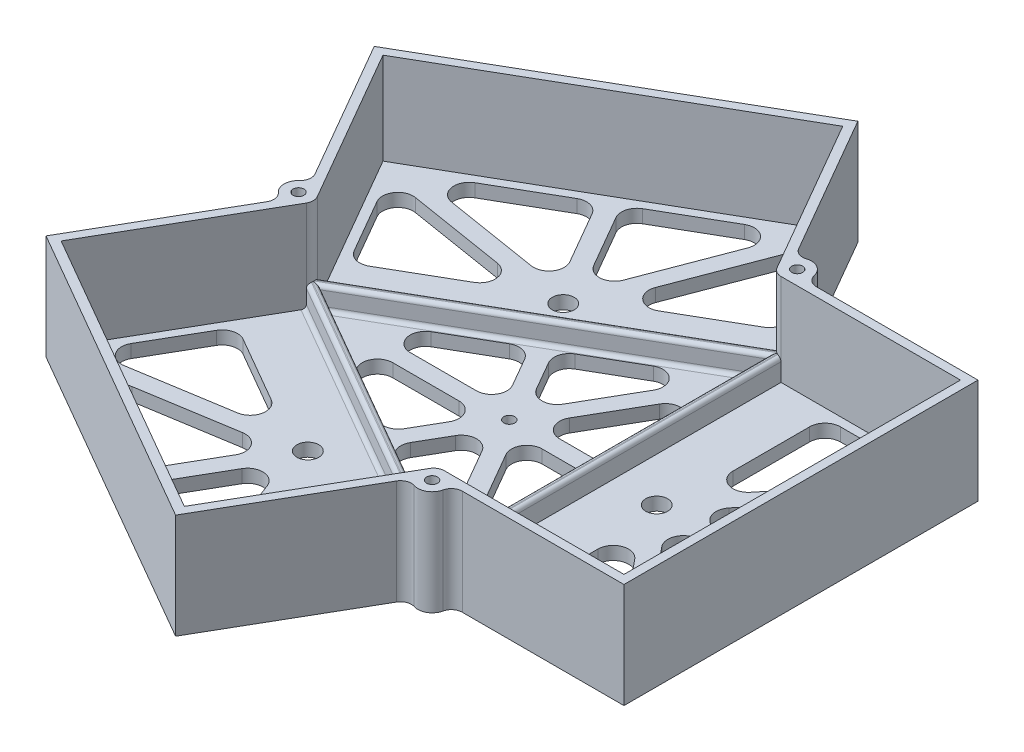
SolidWorks part; units mm, degrees
ref_plane "Front Plane" through (0, 0, 0) normal (0, 0, 1) x (1, 0, 0)
ref_plane "Top Plane" through (0, 0, 0) normal (0, 1, 0) x (1, 0, 0)
ref_plane "Right Plane" through (0, 0, 0) normal (1, 0, 0) x (0, 0, -1)
sketch "Sketch1" plane through (0, 0, 0) normal (0, 1, 0) x (1, 0, 0)
  line L0 (19.5158, -90.1492) -> (5.5625, -53.4677)
  line L5 (23.4295, -18.521) -> (22.1795, -20.6861)
  line L6 (85.5432, -56.1036) -> (56.6565, -56.1036) construction
  line L7 (89.5432, -60.1036) -> (89.5432, 20.8964)
  line L8 (-10.5648, -77.401) -> (24.5092, -97.651)
  line L9 (-27.1955, -27.3848) -> (-27.1955, -21.6036)
  line L10 (-10.5648, -77.401) -> (-45.6389, -57.151)
  line L11 (-45.6389, -57.151) -> (-29.1955, -28.6702)
  line L12 (-45.6389, 17.9439) -> (-29.1955, -10.5369)
  line L13 (24.5092, 58.4439) -> (40.9526, 29.9631)
  line L14 (-27.1955, -19.6036) -> (20.4951, -19.6036)
  line L19 (-45.6389, 17.9439) -> (24.5092, 58.4439)
  line L20 (89.5432, 20.8964) -> (56.6565, 20.8964)
  line L21 (89.5432, -60.1036) -> (56.6565, -60.1036)
  line L22 (24.5092, -97.651) -> (40.9526, -69.1702)
  line L23 (41.0658, 27.5883) -> (46.0725, 24.6977)
  line L24 (5.2031, -46.0901) -> (-27.1955, -27.3848)
  line L25 (47.8045, 23.6977) -> (23.9592, -17.6036)
  line L26 (-29.1955, -28.6702) -> (-29.1955, -10.5369)
  line L27 (0.0674, -47.7438) -> (-26.6748, -32.3042)
  line L28 (58.5432, -25.2243) -> (58.5432, -56.1036)
  line L29 (40.9526, -69.1702) -> (56.6565, -60.1036)
  line L34 (40.9526, 29.9631) -> (56.6565, 20.8964)
  line L35 (54.5432, -21.6036) -> (54.5432, -59.0142)
  line L36 (9.8029, 14.1574) -> (36.5451, 29.5971)
  line L37 (49.5366, 22.6977) -> (54.5432, 19.8071)
  line L38 (54.5432, -59.0142) -> (49.5366, -61.9048)
  line L39 (8.6672, 8.883) -> (41.0658, 27.5883)
  line L40 (47.8045, -62.9048) -> (23.9592, -21.6036)
  line L41 (21.6498, -17.6036) -> (7.2251, 7.3808)
  line L42 (21.5545, -19.6036) -> (24.0545, -19.6036)
  line L43 (21.6498, -21.6036) -> (7.2251, -46.5879)
  line L44 (23.4295, -20.6861) -> (22.1795, -18.521)
  line L45 (-26.6748, -6.9029) -> (0.0674, 8.5367)
  line L46 (58.5432, 16.8964) -> (58.5432, -13.9828)
  line L47 (36.5451, -68.8042) -> (9.8029, -53.3646)
  line L48 (-27.1955, -11.8224) -> (5.2031, 6.883)
  line L49 (54.5432, 19.8071) -> (54.5432, -17.6036)
  line L50 (41.0658, -66.7954) -> (8.6672, -48.0901)
  line L51 (46.0725, 24.6977) -> (22.8045, -15.6036)
  line L52 (-27.1955, -21.6036) -> (19.3404, -21.6036)
  line L53 (49.5366, -61.9048) -> (26.2686, -21.6036)
  line L54 (49.5366, 22.6977) -> (26.2686, -17.6036)
  line L55 (-27.1955, -17.6036) -> (19.3404, -17.6036)
  line L56 (46.0725, -63.9048) -> (22.8045, -23.6036)
  line L57 (25.1139, -19.6036) -> (53.9634, -19.6036)
  line L59 (22.8045, -15.6036) -> (8.6672, 8.883)
  line L60 (26.2686, -17.6036) -> (54.5432, -17.6036)
  line L61 (19.3404, -21.6036) -> (5.2031, -46.0901)
  line L62 (19.3404, -17.6036) -> (5.2031, 6.883)
  line L63 (26.2686, -21.6036) -> (54.5432, -21.6036)
  line L64 (22.8045, -23.6036) -> (8.6672, -48.0901)
  line L71 (-14.9083, -21.6036) -> (10.7782, -36.4337)
  line L73 (43.393, -51.2638) -> (43.393, -21.6036)
  line L75 (39.9289, 14.0567) -> (14.2423, -0.7734)
  line L76 (43.393, -17.6036) -> (43.393, 12.0567)
  line L77 (-39.2552, 14.887) -> (-26.6748, -6.9029)
  line L78 (-36.6455, 18.5174) -> (-10.2969, 33.7297)
  line L79 (23.9646, 51.387) -> (36.5451, 29.5971)
  line L80 (23.9646, -90.5942) -> (36.5451, -68.8042)
  line L81 (-6.8328, -74.9369) -> (19.5158, -90.1492)
  line L82 (-10.2969, -72.9369) -> (-36.6455, -57.7245)
  line L83 (-39.2552, -54.0942) -> (-26.6748, -32.3042)
  line L84 (83.7041, 16.8964) -> (58.5432, 16.8964)
  line L85 (10.7782, -2.7734) -> (-14.9083, -17.6036)
  line L86 (85.5432, -52.0283) -> (85.5432, -21.6036)
  line L87 (83.7041, -56.1036) -> (58.5432, -56.1036)
  line L88 (-8.5648, -73.9369) -> (-40.1748, -55.6869) construction
  line L89 (14.2423, -38.4337) -> (39.9289, -53.2638)
  line L90 (0.0674, -47.7438) -> (-39.2552, -54.0942)
  line L91 (-40.1748, -55.6869) -> (-25.7314, -30.6702) construction
  line L92 (23.0451, -92.1869) -> (37.4885, -67.1702) construction
  line L93 (-8.5648, -73.9369) -> (23.0451, -92.1869) construction
  line L94 (23.9646, -90.5942) -> (9.8029, -53.3646)
  line L95 (-27.1955, -17.6036) -> (-27.1955, -11.8224)
  line L96 (-40.1748, 16.4797) -> (-25.7314, -8.5369) construction
  line L97 (83.7041, 16.8964) -> (58.5432, -13.9828)
  line L98 (46.0725, -63.9048) -> (41.0658, -66.7954)
  line L99 (-40.1748, 16.4797) -> (23.0451, 52.9797) construction
  line L100 (9.8029, 14.1574) -> (23.9646, 51.387)
  line L101 (-39.2552, 14.887) -> (0.0674, 8.5367)
  line L102 (2.0984, -51.4677) -> (-36.6455, -57.7245)
  line L103 (85.5432, 12.8211) -> (60.7527, -17.6036)
  line L104 (60.7527, -21.6036) -> (85.5432, -52.0283)
  line L105 (85.5432, 16.8964) -> (56.6565, 16.8964) construction
  line L106 (5.5625, 14.2605) -> (19.5158, 50.9421)
  line L107 (-36.6455, 18.5174) -> (2.0984, 12.2605)
  line L108 (23.0451, 52.9797) -> (37.4885, 27.9631) construction
  line L109 (85.5432, -56.1036) -> (85.5432, 16.8964) construction
  line L110 (85.5432, -17.6036) -> (85.5432, 12.8211)
  line L111 (58.5432, -25.2243) -> (83.7041, -56.1036)
  line L112 (-6.8328, 35.7297) -> (19.5158, 50.9421)
  line L114 (85.5432, -17.6036) -> (60.7527, -17.6036)
  line L115 (5.5625, 14.2605) -> (-6.8328, 35.7297)
  line L116 (-6.8328, -74.9369) -> (5.5625, -53.4677)
  line L117 (85.5432, -21.6036) -> (60.7527, -21.6036)
  line L118 (2.0984, 12.2605) -> (-10.2969, 33.7297)
  line L119 (-10.2969, -72.9369) -> (2.0984, -51.4677)
  circle A12 centre (5.9352, -48.8222) radius 2.5
  circle A13 centre (5.9352, 9.615) radius 2.5
  circle A14 centre (56.5432, -19.6036) radius 2.5
  circle A15 centre (22.8045, -19.6036) radius 1.25
  point P6 (89.5432, -19.6036)
  point P11 (-10.5648, -77.401)
  point P14 (-10.5648, 38.1939)
  point P15 (-10.5648, -77.401)
  point P26 (-29.1955, -19.6036)
  point P32 (48.8045, -64.6369)
  point P36 (48.8045, 25.4297)
  point P69 (22.8045, -19.6036)
  point P103 (22.8045, -19.6036)
  dimension "D1" = 4
extrude "Boss-Extrude1" add sketch "Sketch1" along normal blind 3 contours L34 L13 L19 L12 L26 L11 L10 L8 L22 L29 L21 L7 L20 A15 A14 A13 A12 L107 L78 L106 L104 L103 | L76 L60 L49 L37 L54 | L75 L51 L23 L39 L59 | L95 L55 L85 L62 L48 | L71 L52 L9 L24 L61 | L98 L56 L89 L64 L50 | L73 L53 L38 L35 L63 region at (73.0998, 0, 58.0386) region at (-8.125, 0, 32.203) region at (27.3579, 0, -13.4819) region at (49.1806, 0, 40.0896) region at (49.1806, 0, -0.8825) region at (-8.125, 0, 7.0042) region at (27.3579, 0, 52.689)
sketch "Sketch2" plane through (0, 3, 0) normal (0, 1, 0) x (1, 0, 0)
  line L0 (-21.6515, -19.6036) -> (-42.9068, 17.2118)
  line L1 (-45.6389, 17.9439) -> (24.5092, 58.4439)
  line L2 (24.5092, 58.4439) -> (40.9526, 29.9631)
  line L3 (40.9526, 29.9631) -> (56.6565, 20.8964)
  line L4 (56.6565, 20.8964) -> (89.5432, 20.8964)
  line L5 (89.5432, 20.8964) -> (89.5432, -60.1036)
  line L6 (89.5432, -60.1036) -> (56.6565, -60.1036)
  line L7 (56.6565, -60.1036) -> (40.9526, -69.1702)
  line L8 (40.9526, -69.1702) -> (24.5092, -97.651)
  line L9 (24.5092, -97.651) -> (-45.6389, -57.151)
  line L10 (-45.6389, -57.151) -> (-29.1955, -28.6702)
  line L11 (-29.1955, -28.6702) -> (-29.1955, -10.5369)
  line L12 (-29.1955, -10.5369) -> (-45.6389, 17.9439)
  line L13 (-42.9068, 17.2118) -> (23.7771, 55.7118)
  line L14 (23.7771, 55.7118) -> (45.0325, 18.8964)
  line L16 (45.0325, 18.8964) -> (87.5432, 18.8964)
  line L17 (87.5432, 18.8964) -> (87.5432, -58.1036)
  line L18 (87.5432, -58.1036) -> (45.0325, -58.1036)
  line L20 (45.0325, -58.1036) -> (23.7771, -94.9189)
  line L21 (23.7771, -94.9189) -> (-42.9068, -56.4189)
  line L22 (-42.9068, -56.4189) -> (-21.6515, -19.6036)
  line L24 (-42.9068, -56.4189) -> (-27.1955, -29.2061) construction
  line L25 (-27.1955, -10.001) -> (-42.9068, 17.2118) construction
  line L26 (23.7771, 55.7118) -> (39.4885, 28.499) construction
  line L27 (56.1206, 18.8964) -> (87.5432, 18.8964) construction
  line L28 (87.5432, -58.1036) -> (56.1206, -58.1036) construction
  line L29 (39.4885, -67.7061) -> (23.7771, -94.9189) construction
  line L30 (-27.1955, -29.2061) -> (-27.1955, -10.001) construction
  line L31 (39.4885, 28.499) -> (56.1206, 18.8964) construction
  line L32 (56.1206, -58.1036) -> (39.4885, -67.7061) construction
  line L33 (-21.6515, -19.6036) -> (-29.1955, -19.6036)
  line L34 (45.0325, 18.8964) -> (48.8045, 25.4297)
  line L35 (45.0325, -58.1036) -> (48.8045, -64.6369)
  circle A0 centre (-25.4235, -19.6036) radius 1.25
  circle A2 centre (46.9185, 22.1631) radius 1.25
  circle A3 centre (46.9185, -61.3702) radius 1.25
  dimension "D1" = 2
extrude "Boss-Extrude2" add sketch "Sketch2" along normal blind 21 contours A2 L34 L3 L33 A0 L0 L13 L14 | A3 L35 L20 L21 L22 L33 A0 L11 | A3 L35 L7 L34 A2 L16 L17 L18 region at (-22.9125, 3, 18.3784) region at (-33.3402, 3, 37.3987) region at (46.5331, 3, -19.4862)
sketch "Sketch4" plane through (0, 24, 0) normal (0, 1, 0) x (1, 0, 0)
  line L0 (-29.1955, -10.5369) -> (-25.8321, -16.3626)
  line L1 (-29.1955, -28.6702) -> (-25.8321, -22.8446)
  line L2 (-29.1955, -28.6702) -> (-29.1955, -10.5369)
  line L3 (40.9526, 29.9631) -> (56.6565, 20.8964)
  line L4 (56.6565, 20.8964) -> (49.9296, 20.8964)
  line L5 (40.9526, 29.9631) -> (44.316, 24.1374)
  line L6 (56.6565, -60.1036) -> (40.9526, -69.1702)
  line L7 (40.9526, -69.1702) -> (44.316, -63.3446)
  line L8 (56.6565, -60.1036) -> (49.9296, -60.1036)
  arc A0 (-25.8321, -16.3626) -> (-25.8321, -22.8446) centre (-25.4235, -19.6036) ccw
  arc A1 (49.9296, 20.8964) -> (44.316, 24.1374) centre (46.9185, 22.1631) ccw
  arc A2 (44.316, -63.3446) -> (49.9296, -60.1036) centre (46.9185, -61.3702) ccw
  point P21 (22.8045, -19.6036)
  dimension "D1" = 3
extrude "Cut-Extrude1" cut sketch "Sketch4" against normal through all
fillet "Fillet1" radius 2.5 9 edges at (45.0325, 13.5, -18.8964) (44.316, 12, -24.1374) (49.9296, 12, -20.8964) (44.316, 12, 63.3446) (49.9296, 12, 60.1036) (45.0325, 13.5, 58.1036) (-21.6515, 13.5, 19.6036) (-25.8321, 12, 22.8446) (-25.8321, 12, 16.3626)
sketch "Sketch5" plane through (0, 3, 0) normal (0, 1, 0) x (1, 0, 0)
  line L0 (-22.3731, -20.8536) -> (44.3108, -59.3536)
  line L1 (46.4759, -58.1036) -> (46.4759, 18.8964)
  line L2 (44.3108, 20.1464) -> (-22.3731, -18.3536)
  line L3 (44.4759, 17.9323) -> (-20.5382, -19.6036)
  line L4 (-20.5382, -19.6036) -> (44.4759, -57.1395)
  line L5 (44.4759, -57.1395) -> (44.4759, 17.9323)
  line L6 (45.3108, 18.4144) -> (-21.3731, -20.0856) construction
  line L7 (-21.3731, -19.1215) -> (45.3108, -57.6215) construction
  line L8 (44.4759, -58.1036) -> (44.4759, 18.8964) construction
  arc A0 (-22.3731, -20.8536) -> (-22.3731, -18.3536) centre (-24.5382, -19.6036) ccw
  arc A1 (44.3108, 20.1464) -> (46.4759, 18.8964) centre (46.4759, 21.3964) ccw
  arc A2 (46.4759, -58.1036) -> (44.3108, -59.3536) centre (46.4759, -60.6036) ccw
  dimension "D1" = 2
extrude "Boss-Extrude3" add sketch "Sketch5" along normal blind 5
fillet "Fillet2" radius 0.9 9 edges at (11.9688, 8, 38.3715) (10.9688, 8, 40.1036) (10.9688, 3, 40.1036) (46.4759, 8, 19.6036) (44.4759, 8, 19.6036) (44.4759, 3, 19.6036) (10.9688, 8, -0.8964) (11.9688, 8, 0.8356) (11.9688, 3, 0.8356)
fillet "Fillet3" radius 3.5 54 edges at (14.2423, 1.5, 38.4337) (43.393, 1.5, 51.2638) (39.9289, 1.5, 53.2638) (-14.9083, 1.5, 21.6036) (10.7782, 1.5, 36.4337) (43.393, 1.5, 21.6036) (43.393, 1.5, 17.6036) (26.2686, 1.5, 17.6036) (26.2686, 1.5, 21.6036) (22.8045, 1.5, 23.6036) (19.3404, 1.5, 21.6036) (22.8045, 1.5, 15.6036) (14.2423, 1.5, 0.7734) (43.393, 1.5, -12.0567) (39.9289, 1.5, -14.0567) (19.3404, 1.5, 17.6036) (-14.9083, 1.5, 17.6036) (10.7782, 1.5, 2.7734) (58.5432, 1.5, -16.8964) (83.7041, 1.5, -16.8964) (85.5432, 1.5, -12.8211) (83.7041, 1.5, 56.1036) (85.5432, 1.5, 52.0283) (85.5432, 1.5, 17.6036) (85.5432, 1.5, 21.6036) (58.5432, 1.5, 25.2243) (60.7527, 1.5, 21.6036) (60.7527, 1.5, 17.6036) (58.5432, 1.5, 13.9828) (58.5432, 1.5, 56.1036) (23.9646, 1.5, 90.5942) (36.5451, 1.5, 68.8042) (19.5158, 1.5, 90.1492) (-6.8328, 1.5, 74.9369) (-10.2969, 1.5, 72.9369) (-36.6455, 1.5, 57.7245) (-39.2552, 1.5, 54.0942) (-26.6748, 1.5, 32.3042) (9.8029, 1.5, 53.3646) (5.5625, 1.5, 53.4677) (2.0984, 1.5, 51.4677) (0.0674, 1.5, 47.7438) (23.9646, 1.5, -51.387) (36.5451, 1.5, -29.5971) (9.8029, 1.5, -14.1574) (5.5625, 1.5, -14.2605) (2.0984, 1.5, -12.2605) (0.0674, 1.5, -8.5367) (19.5158, 1.5, -50.9421) (-6.8328, 1.5, -35.7297) (-10.2969, 1.5, -33.7297) (-26.6748, 1.5, 6.9029) (-36.6455, 1.5, -18.5174) (-39.2552, 1.5, -14.887)
